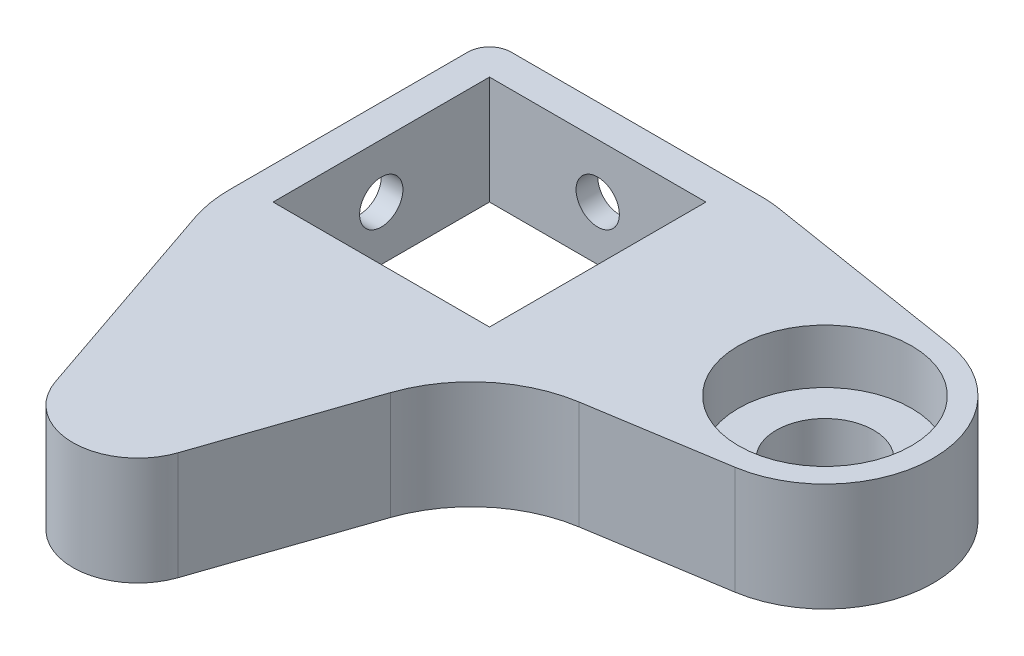
SolidWorks part; units mm, degrees
ref_plane "Front Plane" through (0, 0, 0) normal (0, 0, 1) x (1, 0, 0)
ref_plane "Top Plane" through (0, 0, 0) normal (0, 1, 0) x (1, 0, 0)
ref_plane "Right Plane" through (0, 0, 0) normal (1, 0, 0) x (0, 0, -1)
sketch "Sketch1" plane through (0, 0, 0) normal (0, 1, 0) x (1, 0, 0)
  line L0 (20, 0) -> (41, -10) construction
  line L1 (10, -42.5) -> (0, -20) construction
  line L2 (41, -10) -> (20, -20) construction
  line L3 (0, 0) -> (0, -20) construction
  line L4 (0, 0) -> (20, -20) construction
  line L5 (23.9399, 2.85) -> (42.5764, -0.125)
  line L12 (-3, -23) -> (23, -23) construction
  line L13 (0, 0) -> (20, 0) construction
  line L14 (0, 0) -> (0, -20) construction
  line L15 (0, -20) -> (20, -20) construction
  line L16 (20, 0) -> (20, -20) construction
  line L17 (10, -42.5) -> (20, -20) construction
  line L18 (-3, -21.0074) -> (-3, 1)
  line L19 (-1, 3) -> (22.0482, 3)
  line L20 (23, -23) -> (23, 3) construction
  line L21 (-3, -23) -> (23, 3) construction
  line L22 (-3, 3) -> (23, -23) construction
  line L23 (0, -20) -> (20, -20)
  line L24 (0, -20) -> (0, 0)
  line L25 (0, 0) -> (20, 0)
  line L26 (20, -20) -> (20, 0)
  line L27 (0, -20) -> (20, 0) construction
  line L28 (0, 0) -> (20, -20) construction
  line L29 (30.1306, -21.8617) -> (42.5764, -19.875)
  line L30 (20.6662, -29.8333) -> (15.678, -44.4392)
  line L31 (-2.356, -24.8857) -> (4.322, -44.4392)
  circle A4 centre (10, -42.5) radius 4 construction
  circle A5 centre (41, -10) radius 4 construction
  arc A6 (-3, 1) -> (-1, 3) centre (-1, 1) cw
  circle A7 centre (41, -10) radius 8 construction
  arc A8 (42.5764, -19.875) -> (42.5764, -0.125) centre (41, -10) ccw
  arc A9 (4.322, -44.4392) -> (15.678, -44.4392) centre (10, -42.5) ccw
  arc A10 (30.1306, -21.8617) -> (20.6662, -29.8333) centre (32.0222, -33.7117) ccw
  arc A11 (23.9399, 2.85) -> (22.0482, 3) centre (22.0482, -9) ccw
  arc A12 (-3, -21.0074) -> (-2.356, -24.8857) centre (9, -21.0074) ccw
  point P0 (10, -10)
  point P10 (10, -10)
  dimension "D6" = 8
  dimension "D7" = 16
  dimension "D8" = 20
  dimension "D9" = 12
  dimension "D10" = 12
  dimension "D11" = 12
  dimension "D5" = 2
  dimension "D2" = 20
  dimension "D3" = 3
  dimension "D4" = 42.5
  dimension "D12" = 20
  dimension "D13" = 41
extrude "Boss-Extrude1" add sketch "Sketch1" along normal blind 10
ref_plane "Plane1" through (0, 5, 0) normal (0, 1, 0) x (1, 0, 0)
sketch "Sketch2" plane through (0, 5, 0) normal (0, 1, 0) x (1, 0, 0)
  line L0 (20, 0) -> (41, -10) construction
  line L1 (10, -42.5) -> (0, -20) construction
  line L2 (41, -10) -> (20, -20) construction
  line L3 (0, 0) -> (0, -20) construction
  line L4 (0, 0) -> (20, -20) construction
  line L5 (23.9399, 2.85) -> (42.5764, -0.125) construction
  line L6 (-3, -23) -> (23, -23) construction
  line L7 (0, 0) -> (20, 0) construction
  line L8 (0, 0) -> (0, -20) construction
  line L9 (0, -20) -> (20, -20) construction
  line L10 (20, 0) -> (20, -20) construction
  line L11 (10, -42.5) -> (20, -20) construction
  line L12 (-3, -21.0074) -> (-3, 1) construction
  line L13 (-1, 3) -> (22.0482, 3) construction
  line L14 (23, -23) -> (23, 3) construction
  line L15 (-3, -23) -> (23, 3) construction
  line L16 (-3, 3) -> (23, -23) construction
  line L17 (0, -20) -> (20, -20) construction
  line L18 (0, -20) -> (0, 0) construction
  line L19 (0, 0) -> (20, 0) construction
  line L20 (20, -20) -> (20, 0) construction
  line L21 (0, -20) -> (20, 0) construction
  line L22 (0, 0) -> (20, -20) construction
  line L23 (30.1306, -21.8617) -> (42.5764, -19.875) construction
  line L24 (20.6662, -29.8333) -> (15.678, -44.4392) construction
  line L25 (-2.356, -24.8857) -> (4.322, -44.4392) construction
  circle A0 centre (10, -42.5) radius 4 construction
  circle A1 centre (41, -10) radius 4 construction
  arc A2 (-3, 1) -> (-1, 3) centre (-1, 1) cw construction
  circle A3 centre (41, -10) radius 8
  arc A4 (42.5764, -19.875) -> (42.5764, -0.125) centre (41, -10) ccw construction
  arc A5 (4.322, -44.4392) -> (15.678, -44.4392) centre (10, -42.5) ccw construction
  arc A6 (30.1306, -21.8617) -> (20.6662, -29.8333) centre (32.0222, -33.7117) ccw construction
  arc A7 (23.9399, 2.85) -> (22.0482, 3) centre (22.0482, -9) ccw construction
  arc A8 (-3, -21.0074) -> (-2.356, -24.8857) centre (9, -21.0074) ccw construction
  point P0 (10, -10)
  point P10 (10, -10)
  dimension "D2" = 8
  dimension "D7" = 2
  dimension "D8" = 16
  dimension "D9" = 20
  dimension "D10" = 12
  dimension "D11" = 12
  dimension "D12" = 12
  dimension "D1" = 20
  dimension "D3" = 20
  dimension "D4" = 41
  dimension "D5" = 42.5
  dimension "D6" = 3
extrude "Cut-Extrude2" cut sketch "Sketch2" along normal blind 46
sketch "Sketch3" plane through (0, 5, 0) normal (0, 1, 0) x (1, 0, 0)
  line L0 (20, 0) -> (41, -10) construction
  line L1 (10, -42.5) -> (0, -20) construction
  line L2 (41, -10) -> (20, -20) construction
  line L3 (0, 0) -> (0, -20) construction
  line L4 (0, 0) -> (20, -20) construction
  line L5 (23.9399, 2.85) -> (42.5764, -0.125) construction
  line L6 (-3, -23) -> (23, -23) construction
  line L7 (0, 0) -> (20, 0) construction
  line L8 (0, 0) -> (0, -20) construction
  line L9 (0, -20) -> (20, -20) construction
  line L10 (20, 0) -> (20, -20) construction
  line L11 (10, -42.5) -> (20, -20) construction
  line L12 (-3, -21.0074) -> (-3, 1) construction
  line L13 (-1, 3) -> (22.0482, 3) construction
  line L14 (23, -23) -> (23, 3) construction
  line L15 (-3, -23) -> (23, 3) construction
  line L16 (-3, 3) -> (23, -23) construction
  line L17 (0, -20) -> (20, -20) construction
  line L18 (0, -20) -> (0, 0) construction
  line L19 (0, 0) -> (20, 0) construction
  line L20 (20, -20) -> (20, 0) construction
  line L21 (0, -20) -> (20, 0) construction
  line L22 (0, 0) -> (20, -20) construction
  line L23 (30.1306, -21.8617) -> (42.5764, -19.875) construction
  line L24 (20.6662, -29.8333) -> (15.678, -44.4392) construction
  line L25 (-2.356, -24.8857) -> (4.322, -44.4392) construction
  circle A0 centre (10, -42.5) radius 4
  circle A1 centre (41, -10) radius 4.5
  arc A2 (-3, 1) -> (-1, 3) centre (-1, 1) cw construction
  circle A3 centre (41, -10) radius 8 construction
  arc A4 (42.5764, -19.875) -> (42.5764, -0.125) centre (41, -10) ccw construction
  arc A5 (4.322, -44.4392) -> (15.678, -44.4392) centre (10, -42.5) ccw construction
  arc A6 (30.1306, -21.8617) -> (20.6662, -29.8333) centre (32.0222, -33.7117) ccw construction
  arc A7 (23.9399, 2.85) -> (22.0482, 3) centre (22.0482, -9) ccw construction
  arc A8 (-3, -21.0074) -> (-2.356, -24.8857) centre (9, -21.0074) ccw construction
  point P0 (10, -10)
  point P10 (10, -10)
  dimension "D2" = 8
  dimension "D7" = 2
  dimension "D8" = 16
  dimension "D9" = 20
  dimension "D10" = 12
  dimension "D11" = 12
  dimension "D12" = 12
  dimension "D13" = 9
  dimension "D1" = 20
  dimension "D3" = 20
  dimension "D4" = 41
  dimension "D5" = 42.5
  dimension "D6" = 3
extrude "Cut-Extrude3" cut sketch "Sketch3" against normal blind 10
sketch "Sketch4" plane through (0, 0, -3) normal (0, 0, -1) x (-1, 0, 0)
  line L0 (-20, 10) -> (0, 0) construction
  line L1 (-22.0482, 10) -> (1, 10) construction
  line L2 (-22.0482, 0) -> (1, 0) construction
  line L3 (0, 10) -> (0, 0) construction
  line L4 (-20, 10) -> (-20, 0) construction
  point P5 (-1.1992, -0.2654)
  point P8 (0, 0)
  point P9 (0, 0)
  point P12 (0, 0)
sketch "Sketch5" plane through (-3, 0, 0) normal (-1, 0, 0) x (0, 0, 1)
  line L0 (0, 10) -> (20, 0) construction
  line L1 (-1, 10) -> (21.0074, 10) construction
  line L2 (-1, 0) -> (21.0074, 0) construction
  line L3 (0, 10) -> (0, 0) construction
  line L4 (20, 10) -> (20, 0) construction
  point P12 (10, 5)
hole_wizard "CBORE for M5 Hex Head Bolt1" positions "Sketch5" profile "Sketch6" counterbore size "M5" standard "ANSI Metric"
sketch "Sketch6" plane through (-3, 5, 10) normal (0, 1, 0) x (0, 0, 1)
  line L0 (0, 0) -> (0, 10)
  line L1 (0, 10) -> (2, 10)
  line L2 (2, 10) -> (2, 1)
  line L3 (2, 1) -> (3.5, 1)
  line L4 (3.5, 1) -> (3.5, 0)
  line L5 (3.5, 0) -> (0, 0)
  line L10 (0, 10) -> (-2, 10) construction
  line L11 (0, -6.35) -> (0, 107.95) construction
  dimension "Hole Dia." = 4
  dimension "Hole Depth" = 10
  dimension "C'Bore Dia." = 7
  dimension "C'Bore Depth" = 1
  dimension "Drill Angle" = 180
sketch "Sketch7" plane through (0, 0, -3) normal (0, 0, -1) x (-1, 0, 0)
  line L0 (-20, 10) -> (0, 0) construction
  point P0 (-10, 5)
hole_wizard "CBORE for M5 Hex Head Bolt2" positions "Sketch7" profile "Sketch8" counterbore size "M5" standard "ANSI Metric"
sketch "Sketch8" plane through (10, 5, -3) normal (1, 0, 0) x (0, 1, 0)
  line L0 (0, 0) -> (0, 10)
  line L1 (0, 10) -> (2, 10)
  line L2 (2, 10) -> (2, 1)
  line L3 (2, 1) -> (3.5, 1)
  line L4 (3.5, 1) -> (3.5, 0)
  line L5 (3.5, 0) -> (0, 0)
  line L10 (0, 10) -> (-2, 10) construction
  line L11 (0, -6.35) -> (0, 107.95) construction
  dimension "Hole Dia." = 4
  dimension "Hole Depth" = 10
  dimension "C'Bore Dia." = 7
  dimension "C'Bore Depth" = 1
  dimension "Drill Angle" = 180
